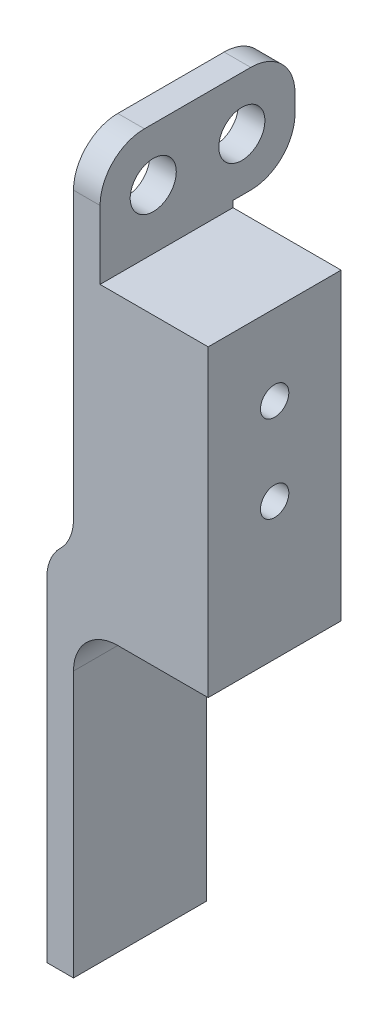
SolidWorks part; units mm, degrees
ref_plane "Front Plane" through (0, 0, 0) normal (0, 0, 1) x (1, 0, 0)
ref_plane "Top Plane" through (0, 0, 0) normal (0, 1, 0) x (1, 0, 0)
ref_plane "Right Plane" through (0, 0, 0) normal (1, 0, 0) x (0, 0, -1)
sketch "Sketch1" plane through (0, 0, 0) normal (1, 0, 0) x (0, 0, -1)
  line L0 (0, 0) -> (10, 0) construction
  line L1 (55, 0) -> (-55, 0) construction
  line L3 (-6, -6) -> (16, -6)
  line L4 (-6, -6) -> (-6, 6)
  line L5 (-6, 6) -> (16, 6)
  line L6 (16, -6) -> (16, 6)
  line L7 (-6, -6) -> (16, 6) construction
  line L8 (-6, 6) -> (16, -6) construction
  circle A0 centre (10, 0) radius 2.6
  circle A1 centre (0, 0) radius 2.6
  point P5 (5, 0)
  dimension "D4" = 5.2
  dimension "D5" = 5.2
  dimension "D1" = 10
  dimension "D2" = 22
  dimension "D3" = 12
extrude "Boss-Extrude1" add sketch "Sketch1" along normal blind 3
sketch "Sketch2" plane through (0, 0, 0) normal (1, 0, 0) x (0, 0, -1)
  line L1 (-6, -6) -> (9, -6)
  line L2 (-6, -6) -> (-6, -42)
  line L3 (-6, -42) -> (9, -42)
  line L4 (9, -6) -> (9, -42)
  dimension "D1" = 15
  dimension "D2" = 36
extrude "Boss-Extrude2" add sketch "Sketch2" along normal blind 3
fillet "Fillet1" radius 5 3 edges at (1.5, 6, 6) (1.5, -6, -16) (1.5, 6, -16)
fillet "Fillet2" radius 1 2 edges at (1.5, -42, 6) (1.5, -42, -9)
sketch "Sketch3" plane through (3, 0, 0) normal (1, 0, 0) x (0, 0, -1)
sketch "Sketch4" plane through (3, 0, 0) normal (1, 0, 0) x (0, 0, -1)
  line L0 (9, -41) -> (9, -6) construction
  line L1 (9, -6.7137) -> (-6, -6.7137)
  line L2 (9, -6.7137) -> (9, -41)
  line L3 (9, -41) -> (-6, -41)
  line L4 (-6, -6.7137) -> (-6, -41)
extrude "Boss-Extrude3" add sketch "Sketch4" along normal blind 12.2
sketch "Sketch7" plane through (0, -41, 0) normal (0, -1, 0) x (-1, 0, 0)
  line L0 (0, 55) -> (0, -55) construction
  line L1 (-15.2, -6) -> (0, -6)
  line L2 (-15.2, -6) -> (-15.2, -8)
  line L3 (-15.2, -8) -> (0, -8)
  line L4 (0, -6) -> (0, -8)
  dimension "D1" = 2
sketch "Sketch9" plane through (0, 0, 0) normal (-1, 0, 0) x (0, 0, 1)
  line L0 (-1.5, -25.5468) -> (-1.5, -15.7468) construction
  circle A0 centre (-1.5, -25.5468) radius 1.6
  circle A1 centre (-1.5, -15.7468) radius 1.6
  dimension "D2" = 3.2
  dimension "D3" = 3.2
  dimension "D1" = 9.8
extrude "Cut-Extrude1" cut sketch "Sketch9" against normal blind 40
sketch "Sketch10" plane through (0, 0, 0) normal (-1, 0, 0) x (0, 0, 1)
  line L0 (-1.5, -25.5468) -> (-1.5, -42) construction
  line L1 (5, -42) -> (-8, -42) construction
sketch "Sketch11" plane through (0, 0, 0) normal (-1, 0, 0) x (0, 0, 1)
  line L1 (6, -41) -> (-9, -41)
  line L2 (6, -41) -> (6, -76)
  line L3 (6, -76) -> (-9, -76)
  line L4 (-9, -41) -> (-9, -76)
  dimension "D1" = 35
sketch "Sketch12" plane through (0, 0, 0) normal (-1, 0, 0) x (0, 0, 1)
  line L0 (-9, -41) -> (-9, -6) construction
  line L1 (-9, -35.7686) -> (6, -35.7686)
  line L2 (-9, -35.7686) -> (-9, -76)
  line L3 (-9, -76) -> (6, -76)
  line L4 (6, -35.7686) -> (6, -76)
extrude "Boss-Extrude5" add sketch "Sketch12" along normal blind 3
fillet "Fillet3" radius 5 1 edges at (0, -35.7686, -1.5)
fillet "Fillet4" radius 5 1 edges at (-3, -35.7686, -1.5)
sketch "Sketch14" plane through (3, 0, 0) normal (1, 0, 0) x (0, 0, -1)
  line L0 (9, -41) -> (9, -76) construction
  line L1 (-6, -41) -> (9, -41)
  line L2 (-6, -41) -> (-6, -42.0244)
  line L3 (-6, -42.0244) -> (9, -42.0244)
  line L4 (9, -41) -> (9, -42.0244)
extrude "Cut-Extrude2" cut sketch "Sketch14" against normal blind 3
fillet "Fillet5" radius 5 1 edges at (0, -41, -1.5)
